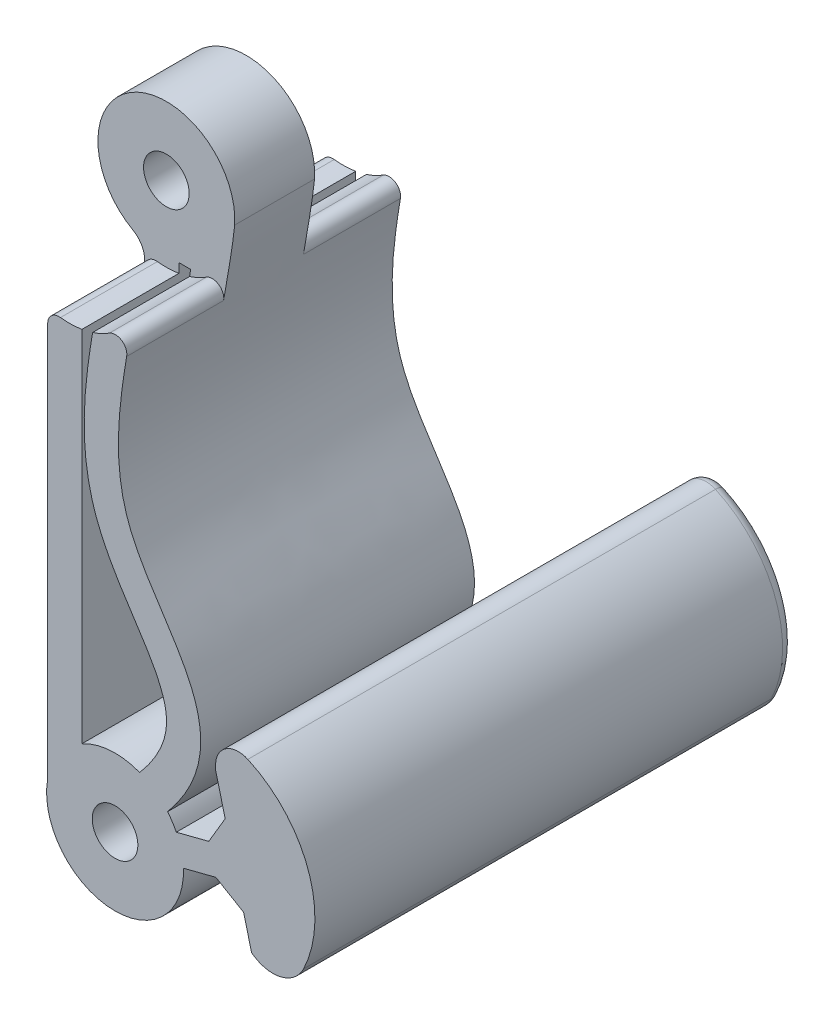
SolidWorks part; units mm, degrees
ref_plane "Front Plane" through (0, 0, 0) normal (0, 0, 1) x (1, 0, 0)
ref_plane "Top Plane" through (0, 0, 0) normal (0, 1, 0) x (1, 0, 0)
ref_plane "Right Plane" through (0, 0, 0) normal (1, 0, 0) x (0, 0, -1)
sketch "Sketch1" plane through (0, 0, 0) normal (0, 0, 1) x (1, 0, 0)
  line L3 (0.9027, 23.1193) -> (0.9027, 44.7293) construction
  line L4 (0.9027, 44.7293) -> (-1.0973, 44.7293) construction
  line L5 (-2.0488, 41.8842) -> (-2.0488, 23.6567)
  line L6 (-0.0313, 41.8842) -> (-0.5488, 41.8842)
  line L7 (-0.5488, 41.8842) -> (-0.5488, 25.7448)
  line L10 (-0.5488, 43.3332) -> (-0.5488, 23.4977) construction
  line L12 (1003.2054, 25.0421) -> (3.2054, 25.0421) construction
  line L13 (-2.0488, 41.8842) -> (49997.9512, 41.8842) construction
  line L14 (-0.5488, 25.0421) -> (-49996.7946, 25.0421) construction
  arc A0 (-2.0488, 41.8842) -> (1.896, 44.5297) centre (-1.0973, 44.7293) cw
  arc A2 (-2.0488, 23.6567) -> (3.2054, 25.0421) centre (0.9027, 23.1193) ccw
  circle A3 centre (-1.0973, 44.7293) radius 1
  circle A4 centre (0.9027, 23.1193) radius 1
  arc A7 (-0.5488, 23.4977) -> (0.9027, 24.6193) centre (0.9027, 23.1193) ccw construction
  arc A8 (-0.5488, 43.3332) -> (0.4006, 44.6513) centre (-1.0973, 44.7293) cw construction
  arc A9 (1.9829, 25.918) -> (-0.5488, 25.7448) centre (0.9027, 23.1193) ccw
  spline S0 degree 3 poles (1.896, 44.5297) (1.6161, 41.7589) (-0.9369, 33.9552) (6.8447, 29.4175) (3.2054, 25.0421) knots 0 0 0 0 0.461185 1 1 1 1
  spline S1 degree 1 poles (0.4006, 44.6513) (0.9027, 24.6193) knots 0 0 1 1 construction
  spline S2 degree 3 poles (0.4006, 44.6513) (0.3814, 44.4652) (0.3367, 44.1044) (0.2163, 43.3069) (0.0657, 42.4502) (-0.0914, 41.5355) (-0.2432, 40.5851) (-0.402, 39.3533) (-0.4791, 37.8282) (-0.3759, 36.2754) (0.01, 34.6811) (0.9413, 32.7707) (2.0354, 31.2469) (2.8047, 29.9095) (3.1286, 29.0309) (3.1964, 28.2674) (3.0323, 27.5503) (2.6663, 26.8291) (2.3349, 26.3502) (2.1068, 26.0672) (2.0129, 25.9541) (1.9549, 25.8844) (1.8019, 25.7008) (1.4593, 25.2881) (1.1253, 24.887) (0.9027, 24.6193) knots 0.001801 0.001801 0.001801 0.001801 0.034767 0.067734 0.132717 0.165683 0.1996 0.265533 0.331467 0.3974 0.463333 0.529266 0.661132 0.727066 0.792999 0.858932 0.924865 0.957832 0.990798 0.99904 1.001358 1.005479 1.00754 1.023765 1.056732 1.056732 1.056732 1.056732 only from (-0.0313, 41.8842) to (1.9829, 25.918)
  dimension "D2" = 3
  dimension "D3" = 21.61
  dimension "D4" = 2
  dimension "D5" = 1.5
  dimension "D6" = 6
  dimension "D7" = 1.5
extrude "Boss-Extrude1" add sketch "Sketch1" along normal blind 12
ref_plane "midplane" through (0, 0, 6) normal (0, 0, 1) x (1, 0, 0)
sketch "Sketch2" plane through (0, 0, 12) normal (0, 0, 1) x (1, 0, 0)
  circle A4 centre (-1.0973, 44.7293) radius 3.3
  dimension "D1" = 6.6
extrude "Cut-Extrude1" cut sketch "Sketch2" against normal blind 4.25
mirror "Mirror1" about plane through (0, 0, 6) normal (0, 0, 1) of "Cut-Extrude1"
sketch "Sketch3" plane through (0, 0, 6) normal (0, 0, 1) x (1, 0, 0)
  circle A2 centre (0.9027, 23.1193) radius 3.3
  dimension "D1" = 6.6
extrude "Cut-Extrude2" cut sketch "Sketch3" against normal blind 2.25 and the other way blind 2.25
ref_plane "Plane1" through (9.4512, 0, 0) normal (1, 0, 0) x (0, 0, -1)
sketch "Sketch6" plane through (0, 0, 0) normal (0, 0, 1) x (1, 0, 0)
  line L1 (4.6597, 28.4574) -> (-2.0488, 28.4574) construction
  line L2 (-2.0488, 41.5694) -> (-2.0488, 23.6567) construction
  line L4 (8.1477, 20.6439) -> (6.8888, 21.5287)
  line L5 (5.3117, 27.6705) -> (5.3117, 29.1888)
  arc A0 (5.3117, 29.1888) -> (8.1477, 20.6439) centre (4.6644, 24.2309) cw
  arc A1 (5.3117, 27.6705) -> (6.8888, 21.5287) centre (4.6644, 24.2309) cw
  dimension "D1" = 5
  dimension "D2" = 3.5
extrude "Boss-Extrude4" add sketch "Sketch6" along normal up to surface (12 mm away) and the other way blind 9 up to face at (0.5703, 30.8825, 12)
sketch "Sketch7" plane through (0, 0, 12) normal (0, 0, 1) x (1, 0, 0)
  line L3 (5.3117, 27.6705) -> (6.8888, 21.5287)
  arc A0 (6.8888, 21.5287) -> (5.3117, 27.6705) centre (4.6644, 24.2309) ccw construction
  arc A1 (6.8888, 21.5287) -> (5.3117, 27.6705) centre (4.6644, 24.2309) ccw
extrude "Boss-Extrude5" add sketch "Sketch7" against normal up to surface (21 mm away) up to face at (7.5736, 25.1058, -9)
sketch "Sketch8" plane through (0, 0, 12) normal (0, 0, 1) x (1, 0, 0)
  line L5 (0.9027, 23.1193) -> (6.1353, 24.463) construction
  line L6 (5.3117, 27.6705) -> (6.8888, 21.5287) construction
  line L7 (6.1353, 24.463) -> (5.9799, 25.0683)
  line L8 (5.9799, 25.0683) -> (3.2621, 24.3704)
  line L9 (3.2621, 24.3704) -> (3.573, 23.1597)
  line L10 (3.573, 23.1597) -> (6.2908, 23.8576)
  line L11 (6.2908, 23.8576) -> (6.1353, 24.463)
  line L12 (5.3117, 27.6705) -> (6.8888, 21.5287) construction
  line L13 (5.3117, 27.6705) -> (6.8888, 21.5287) construction
  dimension "D1" = 1.25
extrude "Boss-Extrude6" add sketch "Sketch8" against normal up to surface (3.75 mm away) up to face at (1.9027, 23.1193, 8.25)
sketch "Sketch10" plane through (0, 0, 0) normal (0, 0, -1) x (-1, 0, 0)
  line L8 (-3.2621, 24.3704) -> (-3.573, 23.1597) construction
  line L9 (-3.573, 23.1597) -> (-6.2908, 23.8576) construction
  line L10 (-6.2908, 23.8576) -> (-6.1353, 24.463) construction
  line L11 (-6.1353, 24.463) -> (-5.9799, 25.0683) construction
  line L12 (-5.9799, 25.0683) -> (-3.2621, 24.3704) construction
  line L13 (-3.2621, 24.3704) -> (-3.573, 23.1597)
  line L14 (-3.573, 23.1597) -> (-6.2908, 23.8576)
  line L15 (-6.2908, 23.8576) -> (-6.1353, 24.463)
  line L16 (-6.1353, 24.463) -> (-5.9799, 25.0683)
  line L17 (-5.9799, 25.0683) -> (-3.2621, 24.3704)
extrude "Boss-Extrude7" add sketch "Sketch10" against normal up to surface (3.75 mm away) up to face at (1.9027, 23.1193, 3.75)
fillet "Fillet1" radius 0.5 4 edges at (-2.0488, 41.5694, 2.125) (-2.0488, 41.5694, 9.875) (1.6708, 42.9328, 2.125) (1.6708, 42.9328, 9.875)
fillet "Fillet2" radius 1 1 edges at (-2.0488, 41.8842, 6)
fillet "Fillet10" radius 1.5 1 edges at (8.1477, 20.6439, 1.5)
fillet "Fillet11" radius 1 1 edges at (-2.0488, 24.5953, 6)
chamfer "Chamfer5" distance 1 angle 45 7 edges at (5.9799, 25.0683, 10.125) (6.1353, 24.463, 8.25) (6.2908, 23.8576, 10.125) (6.1353, 24.463, 3.75) (5.9799, 25.0683, 1.875) (6.2908, 23.8576, 1.875) (6.1353, 24.463, 0)
fillet "Fillet12" radius 1 1 edges at (5.3117, 29.1888, 1.5)
fillet "Fillet13" radius 0.5 5 edges at (6.9215, 21.5058, -9) (8.194, 21.2582, -9) (5.3117, 27.7732, -9) (5.7694, 28.7161, -9) (9.364, 25.9379, -9)
equation "\"axle-diameter\"=2"
equation "\"switch-thickness\"=12"
equation "\"base-width\"=4.0"
equation "\"axle-bushing-radius\"=3"
equation "\"D1@Sketch1\"=\"axle-diameter\""
equation "\"D2@Sketch1\"=\"axle-bushing-radius\""
equation "\"D1@Cut-Extrude1\"=\"switch-thickness\"/3+\"clearance\""
equation "\"D1@Cut-Extrude2\"=\"switch-thickness\"/6+\"clearance\""
equation "\"D2@Cut-Extrude2\"=\"switch-thickness\"/6+\"clearance\""
equation "\"D1@Boss-Extrude1\"=\"switch-thickness\""
equation "\"D1@Sketch2\"=\"axle-bushing-radius\"*2.2"
equation "\"D1@Sketch3\"=\"axle-bushing-radius\"*2.2"
equation "\"clearance\"= 0.25"
equation "\"arm-width\"=3.0"
equation "\"min-diameter\"=70"
